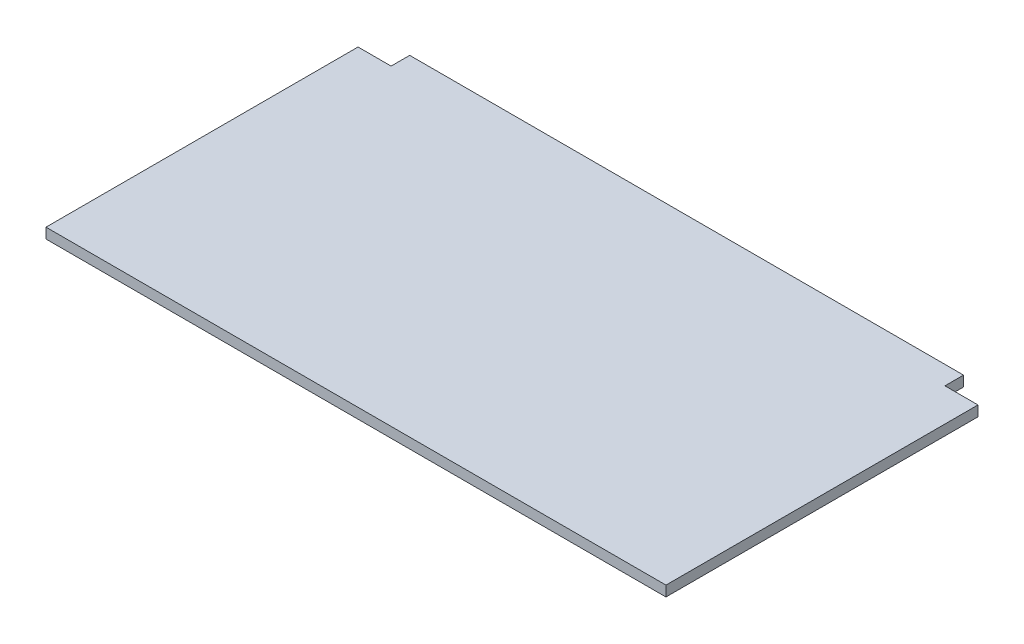
SolidWorks part; units mm, degrees
material "Cedar"
ref_plane "Front Plane" through (0, 0, 0) normal (0, 0, 1) x (1, 0, 0)
ref_plane "Top Plane" through (0, 0, 0) normal (0, 1, 0) x (1, 0, 0)
ref_plane "Right Plane" through (0, 0, 0) normal (1, 0, 0) x (0, 0, -1)
sketch "Sketch1" plane through (0, 0, 0) normal (0, 1, 0) x (1, 0, 0)
  line L1 (750, -400) -> (-750, -400)
  line L2 (750, -400) -> (750, 400)
  line L3 (750, 400) -> (-750, 400)
  line L4 (-750, -400) -> (-750, 400)
  line L5 (750, -400) -> (-750, 400) construction
  line L6 (750, 400) -> (-750, -400) construction
  point P0 (0, 0)
  dimension "D1" = 800
  dimension "D2" = 1500
extrude "Boss-Extrude1" add sketch "Sketch1" along normal blind 25
sketch "Sketch2" plane through (0, 25, 0) normal (0, 1, 0) x (1, 0, 0)
  line L0 (750, 400) -> (-750, 400) construction
  line L1 (-761.4719, 422.6992) -> (-670, 422.6992)
  line L2 (-761.4719, 422.6992) -> (-761.4719, 355)
  line L3 (-761.4719, 355) -> (-670, 355)
  line L4 (-670, 422.6992) -> (-670, 355)
  line L5 (777.3454, 416.3957) -> (670, 416.3957)
  line L6 (777.3454, 416.3957) -> (777.3454, 355)
  line L7 (777.3454, 355) -> (670, 355)
  line L8 (670, 416.3957) -> (670, 355)
  line L9 (-750, 400) -> (-750, -400) construction
  line L10 (750, -400) -> (750, 400) construction
  line M5 (-750, 400) -> (-750, -400)
  line M7 (750, -400) -> (750, 400)
  line M8 (750, 400) -> (-750, 400)
  dimension "D1" = 45
  dimension "D2" = 80
  dimension "D3" = 80
extrude "Cut-Extrude1" cut sketch "Sketch2" against normal through all contours L4 L3 M8 M5 | L8 L7 M8 M7 region at (710, 25, -377.5) region at (-710, 25, -377.5)
equation "\"D3@Sketch2\"=\"D2@Sketch2\""
equation "\"TableThickness\" = \"Thickness@Boss-Extrude1\""
